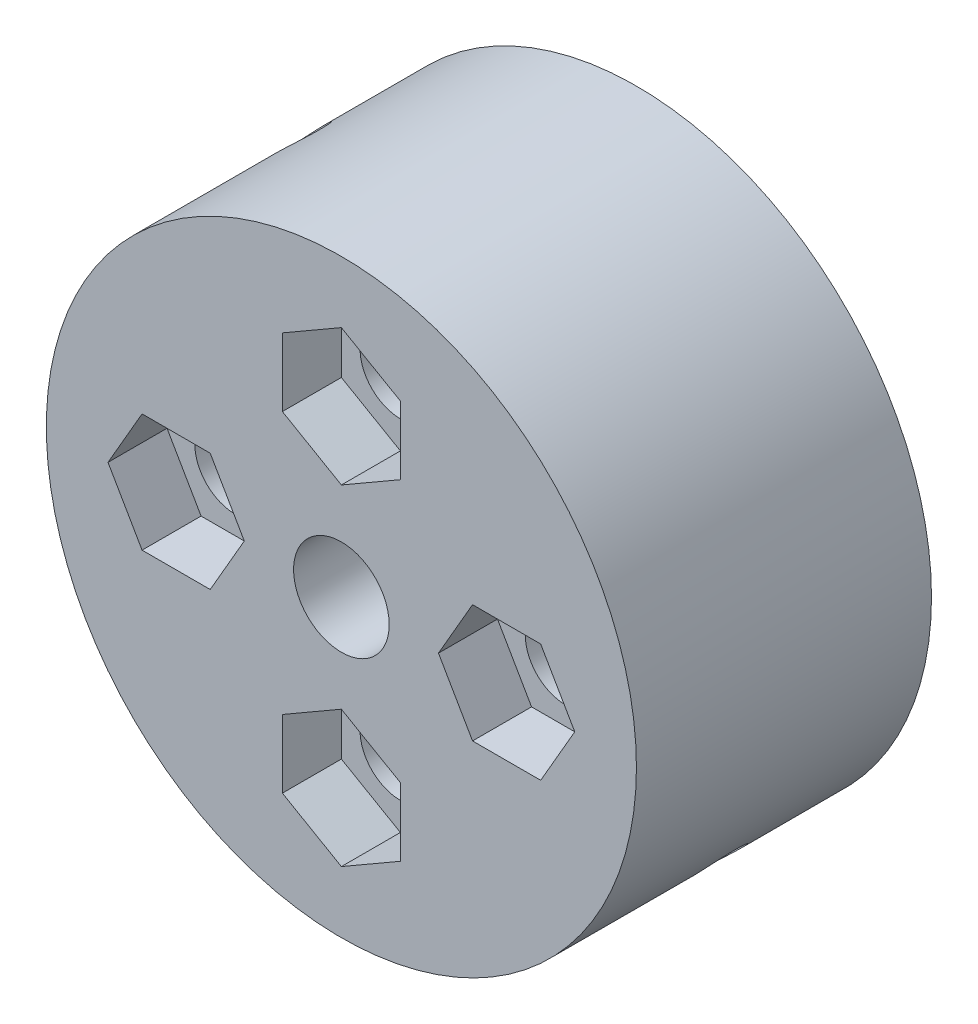
SolidWorks part; units mm, degrees
material "ABS"
ref_plane "Front Plane" through (0, 0, 0) normal (0, 0, 1) x (1, 0, 0)
ref_plane "Top Plane" through (0, 0, 0) normal (0, 1, 0) x (1, 0, 0)
ref_plane "Right Plane" through (0, 0, 0) normal (1, 0, 0) x (0, 0, -1)
sketch "Sketch1" plane through (0, 0, 0) normal (0, 0, 1) x (1, 0, 0)
  circle A0 centre (0, 0) radius 12.5
  dimension "D1" = 25
extrude "Boss-Extrude1" add sketch "Sketch1" along normal blind 12.5
sketch "Sketch2" plane through (0, 0, 12.5) normal (0, 0, 1) x (1, 0, 0)
  line L1 (0, 9.8868) -> (-2.5, 8.4434)
  line L2 (-2.5, 8.4434) -> (-2.5, 5.5566)
  line L3 (-2.5, 5.5566) -> (0, 4.1132)
  line L4 (0, 4.1132) -> (2.5, 5.5566)
  line L5 (2.5, 5.5566) -> (2.5, 8.4434)
  line L6 (2.5, 8.4434) -> (0, 9.8868)
  circle A0 centre (0, 7) radius 2.5 construction
  circle A1 centre (0, 7) radius 1.71
  dimension "D2" = 5
  dimension "D3" = 3.42
  dimension "D1" = 7
extrude "Cut-Extrude1" cut sketch "Sketch2" against normal blind 2.5 contours L5 L6 L1 L2 L3 L4 A1 | A1 | A1 | L1 L2 L3 L4 L5 L6 region at (1.2118, 9.0989, 12.5) region at (0, 7, 12.5)
extrude "Cut-Extrude2" cut sketch "Sketch2<3>" against normal up to next contours A1 region at (0, 7, 12.5)
sketch "Sketch2<3>" plane through (0, 0, 12.5) normal (0, 0, 1) x (1, 0, 0) same geometry as "Sketch2"
pattern_circular "CirPattern1" count 4 every 90 about axis through (0, 0, 12.5) along (0, 0, -1) of "Cut-Extrude1", "Cut-Extrude2"
sketch "Sketch3" plane through (0, 0, 12.5) normal (0, 0, 1) x (1, 0, 0)
  circle A0 centre (0, 0) radius 2.025
  dimension "D1" = 4.05
extrude "Cut-Extrude3" cut sketch "Sketch3" against normal up to next
ref_plane "Plane1" through (0, 0, 0) normal (-0.7071, 0.7071, 0) x (0.7071, 0.7071, 0)
sketch "Sketch6" plane through (0, 0, 0) normal (-0.7071, 0.7071, 0) x (0.7071, 0.7071, 0)
  circle A0 centre (0, -5.41) radius 1.08
  dimension "D1" = 2.16
  dimension "D2" = 5.41
extrude "Cut-Extrude5" cut sketch "Sketch6" against normal through all both and the other way through all
